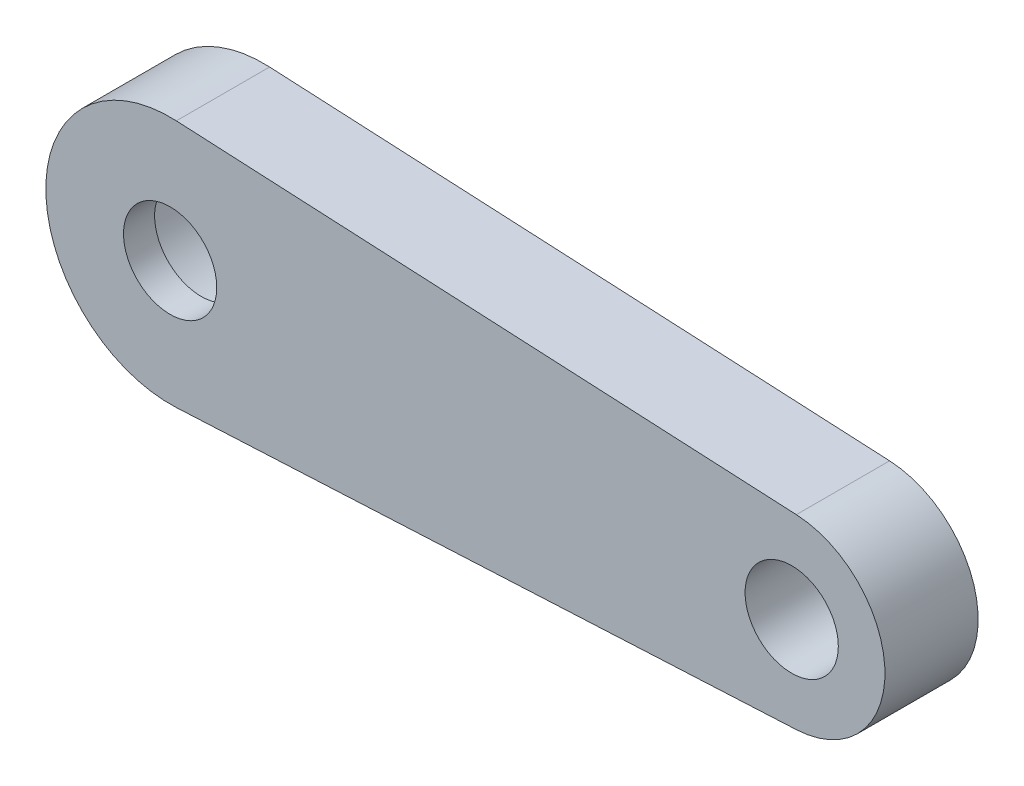
SolidWorks part; units mm, degrees
ref_plane "Plan de face" through (0, 0, 0) normal (0, 0, 1) x (1, 0, 0)
ref_plane "Plan de dessus" through (0, 0, 0) normal (0, 1, 0) x (1, 0, 0)
ref_plane "Plan de droite" through (0, 0, 0) normal (1, 0, 0) x (0, 0, -1)
sketch "Esquisse1" plane through (0, 0, 0) normal (0, 0, 1) x (1, 0, 0)
  line L0 (0.2, 3.995) -> (20.15, 2.9962)
  line L3 (20.15, -2.9962) -> (0.2, -3.995)
  arc A2 (0.2, 3.995) -> (0.2, -3.995) centre (0, 0) ccw
  arc A3 (20.15, 2.9962) -> (20.15, -2.9962) centre (20, 0) cw
  circle A4 centre (0, 0) radius 1.5
  circle A5 centre (20, 0) radius 1.5
  circle A6 centre (0, 0) radius 2.5
  dimension "D1" = 3
  dimension "D2" = 4
  dimension "D3" = 3
  dimension "D5" = 3
  dimension "D6" = 5
  dimension "D4" = 20
extrude "Boss.-Extru.1" add sketch "Esquisse1" along normal blind 3 contours A3 L0 A2 L3 A6 A5 | A6 A4 region at (9.5044, 0, 0) region at (-2.4293, 0, 0)
extrude "Enlèv. mat.-Extru.1" cut sketch "Esquisse1<4>" along normal blind 2 contours A6 A4 region at (-2.4293, 0, 0)
sketch "Esquisse1<4>" plane through (0, 0, 0) normal (0, 0, 1) x (1, 0, 0) same geometry as "Esquisse1"
